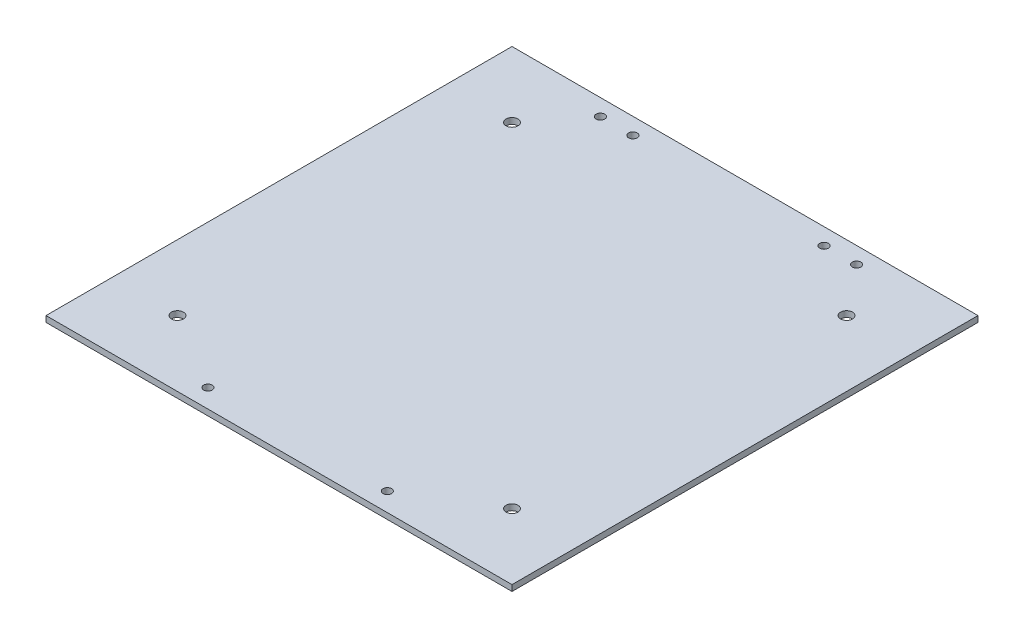
SolidWorks part; units mm, degrees
ref_plane "Front Plane" through (0, 0, 0) normal (0, 0, 1) x (1, 0, 0)
ref_plane "Top Plane" through (0, 0, 0) normal (0, 1, 0) x (1, 0, 0)
ref_plane "Right Plane" through (0, 0, 0) normal (1, 0, 0) x (0, 0, -1)
sketch "Sketch1" plane through (0, 0, 0) normal (0, 1, 0) x (1, 0, 0)
  line L1 (0, 0) -> (247.65, 0)
  line L2 (0, 0) -> (0, 247.65)
  line L3 (0, 247.65) -> (247.65, 247.65)
  line L4 (247.65, 0) -> (247.65, 247.65)
  dimension "D1" = 247.65
  dimension "D2" = 247.65
extrude "Boss-Extrude1" add sketch "Sketch1" along normal blind 3.175
sketch "Sketch2" plane through (0, 3.175, 0) normal (0, 1, 0) x (1, 0, 0)
  line L0 (58.039, 238.8616) -> (70.739, 238.8616) construction
  line L1 (176.911, 238.8616) -> (189.611, 238.8616) construction
  line L2 (247.65, 247.65) -> (0, 247.65) construction
  line L3 (0, 0) -> (247.65, 0) construction
  line L4 (0, 247.65) -> (0, 0) construction
  line L5 (247.65, 0) -> (247.65, 247.65) construction
  circle A0 centre (55.753, 238.8616) radius 2.286
  circle A1 centre (73.025, 238.8616) radius 2.286
  circle A2 centre (174.625, 238.8616) radius 2.286
  circle A3 centre (191.897, 238.8616) radius 2.286
  circle A4 centre (76.1568, 9.906) radius 2.286
  circle A5 centre (171.4932, 9.906) radius 2.286
  point P14 (123.825, 247.65)
  dimension "D3" = 4.572
  dimension "D7" = 4.572
  dimension "D10" = 76.1568
  dimension "D1" = 12.7
  dimension "D2" = 12.7
  dimension "D4" = 8.7884
  dimension "D5" = 50.8
  dimension "D6" = 50.8
  dimension "D8" = 9.906
  dimension "D9" = 76.1568
extrude "Cut-Extrude1" cut sketch "Sketch2" against normal through all
sketch "Sketch3" plane through (0, 3.175, 0) normal (0, 1, 0) x (1, 0, 0)
  line L0 (247.65, 0) -> (0, 247.65) construction
  line L1 (247.65, 247.65) -> (0, 247.65) construction
  line L2 (247.65, 0) -> (247.65, 247.65) construction
  circle A0 centre (212.725, 212.725) radius 3.175
  circle A1 centre (212.725, 34.925) radius 3.175
  circle A2 centre (34.925, 34.925) radius 3.175
  circle A3 centre (34.925, 212.725) radius 3.175
  point P10 (123.825, 123.825)
  dimension "D1" = 6.35
  dimension "D2" = 34.925
  dimension "D3" = 34.925
  dimension "D5" = 177.8
  dimension "D6" = 125.7236
  dimension "D4" = 4
extrude "Cut-Extrude2" cut sketch "Sketch3" against normal through all
